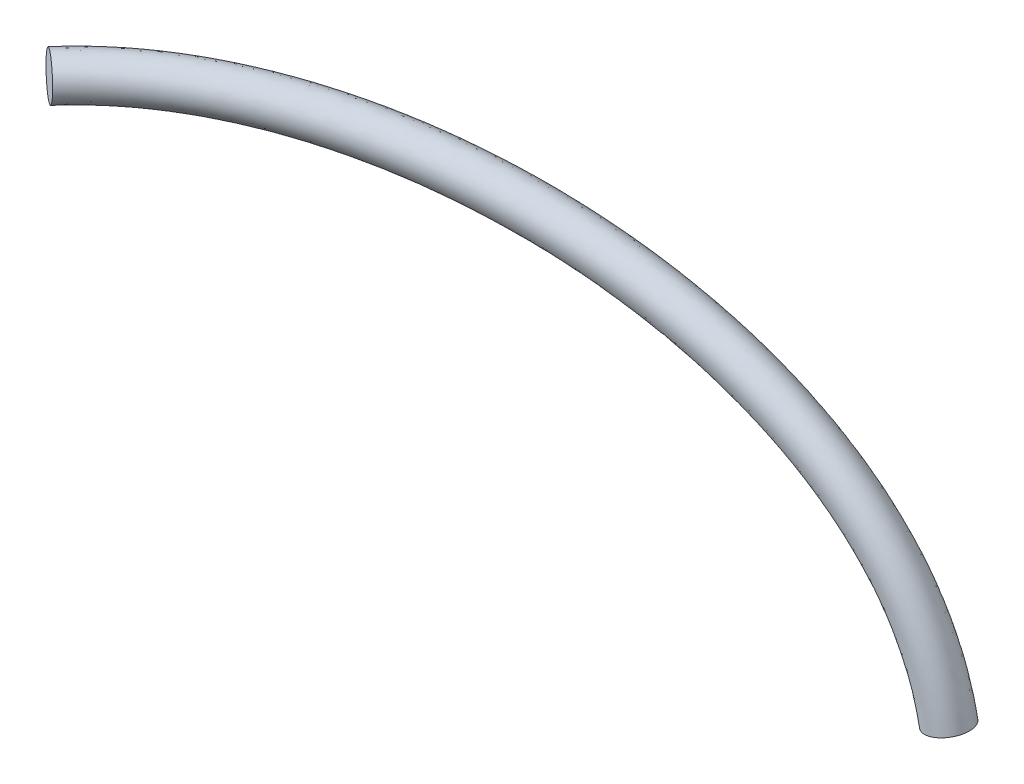
SolidWorks part; units mm, degrees
ref_plane "X-Y Datum" through (0, 0, 0) normal (0, 0, 1) x (1, 0, 0)
ref_plane "X-Z Datum" through (0, 0, 0) normal (0, 1, 0) x (1, 0, 0)
ref_plane "Y-Z Datum" through (0, 0, 0) normal (1, 0, 0) x (0, 0, -1)
sketch3d "3DSketch1"
  spline S0 degree 2 poles (140.461, 313.7571, 626.4781) (100.9347, 306.5353, 599.239) (93.515, 273.6004, 594.1184) knots 0 0 0 0.40389 0.40389 0.40389
sweep "Sweep1" [suppressed] add path "3DSketch1" circular profile diameter 8.001 parameters "D3"=8.001
sketch3d "3DSketch4"
  spline S0 degree 3 poles (597.3278, 269.1305, 593.3322) (586.8049, 321.2158, 593.1385) (500.0142, 332.4473, 596.4483) (467.864, 333.7172, 636.536) knots 0 0 0 0 1 1 1 1
sweep "Sweep4" add path "3DSketch4" circular profile diameter 8.001 parameters "D3"=8.001
